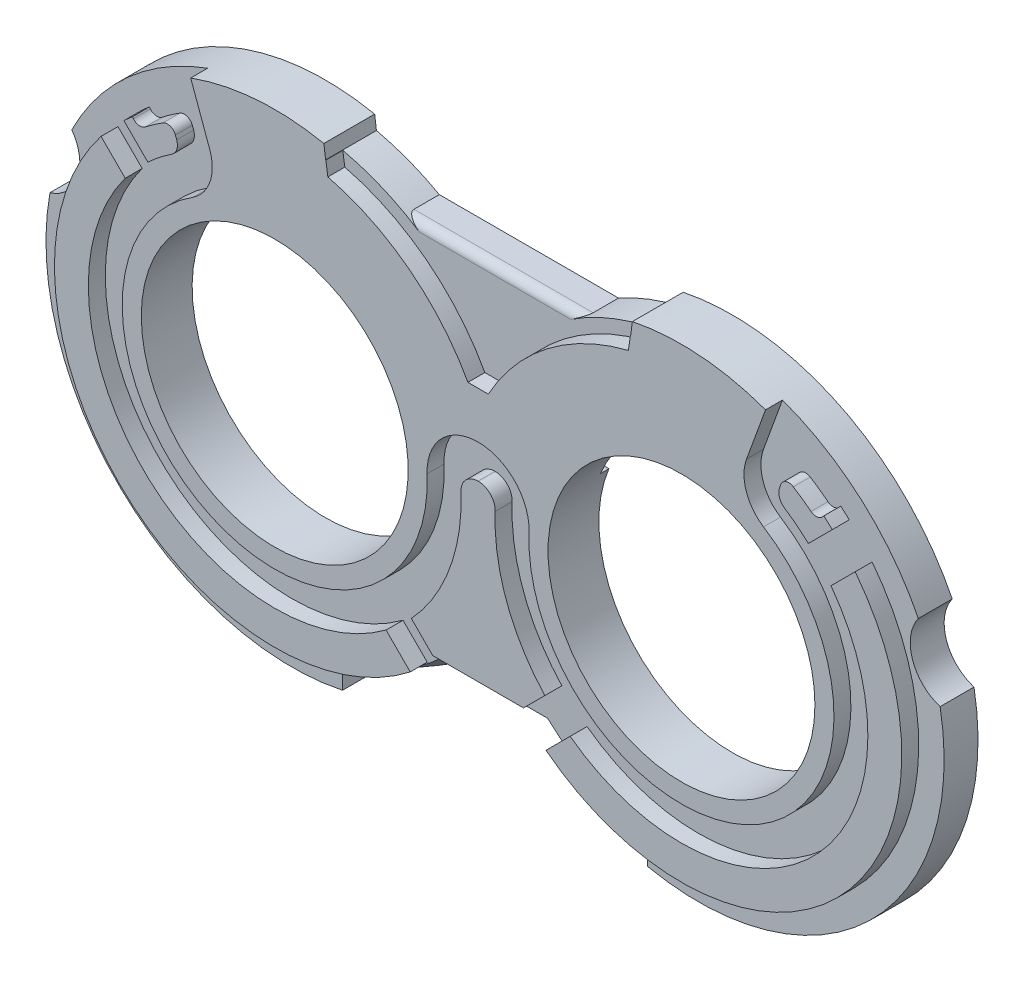
SolidWorks part; units mm, degrees
material "PW70:6:C1:0:1:2:Re:26:"
ref_plane "Plan1" through (0, 0, 0) normal (0, 0, 1) x (1, 0, 0)
ref_plane "Plan2" through (0, 0, 0) normal (0, 1, 0) x (1, 0, 0)
ref_plane "Plan3" through (0, 0, 0) normal (1, 0, 0) x (0, 0, -1)
sketch "Esquisse1" plane through (0, 0, 0) normal (0, 0, 1) x (1, 0, 0)
  line L0 (0, 24) -> (10.5743, 24)
  line L1 (0, -20.5) -> (5.6697, -20.5)
  line L2 (0, 24) -> (0, -20.5)
  line L5 (18, -26.8375) -> (18, -28.3725)
  line L6 (18, 26.8375) -> (18.2039, 28.4149)
  arc A0 (18, 26.8375) -> (10.5743, 24) centre (24, 0) ccw
  circle A1 centre (24, 0) radius 15.75
  arc A2 (5.6697, -20.5) -> (18, -26.8375) centre (24, 0) ccw
  arc A3 (18, -28.3725) -> (52.5259, 5.2222) centre (24, 0) ccw
  arc A4 (49.9541, 12.9378) -> (52.5259, 5.2222) centre (54, 10) ccw
  arc A5 (49.9541, 12.9378) -> (18.2039, 28.4149) centre (24, 0) ccw
  dimension "D1" = 10
  dimension "D3" = 31.5
  dimension "D4" = 54
  dimension "D6" = 55
  dimension "D2" = 24
extrude "Base-Extrusion" add sketch "Esquisse1" along normal blind 6
sketch "Esquisse3" plane through (0, 0, 6) normal (0, 0, 1) x (1, 0, 0)
  line L0 (0, 12.5) -> (0, -20.5)
  line L1 (0, -20.5) -> (8.0078, -20.5)
  line L2 (0, 12.5) -> (1.202, 12.5)
  line L4 (24, 0) -> (60, 0) construction
  line L5 (32.8925, 24.432) -> (33.9186, 27.2511)
  line L6 (18.2039, 28.4149) -> (17.7311, 25.2329)
  arc A0 (8.0078, -20.5) -> (32.8925, 24.432) centre (24, 0) ccw
  arc A1 (33.9186, 27.2511) -> (18.2039, 28.4149) centre (24, 0) ccw
  arc A2 (17.7311, 25.2329) -> (1.202, 12.5) centre (24, 0) ccw
  dimension "D1" = 52
  dimension "D2" = 33
  dimension "D3" = 70
extrude "Enlèv. mat.-Extru.1" cut sketch "Esquisse3" against normal blind 2 flip side to cut
sketch "Esquisse4" plane through (0, 0, 6) normal (0, 0, 1) x (1, 0, 0)
  line L0 (0, 7) -> (0.0208, 7)
  line L1 (10.5743, 24) -> (0, 24) construction
  line L2 (0, 3) -> (0.0208, 3)
  line L3 (24, 0) -> (80, 0) construction
  line L4 (5.351, -17.5) -> (7.8797, -14.9712)
  line L5 (0, -17.5) -> (5.351, -17.5)
  line L6 (8.0078, -20.5) -> (0, -20.5)
  line L7 (0, -20.5) -> (8.0078, -20.5) construction
  line L8 (8.0078, -20.5) -> (10.8617, -17.6461)
  line L9 (32.8925, 24.432) -> (31.6783, 21.096)
  line L10 (0, 7) -> (0, 3)
  line L11 (0, -17.5) -> (0, -20.5)
  line L12 (41.8013, 18.9503) -> (38.9712, 16.1203)
  line L13 (40.6777, 19.7061) -> (40.7942, 19.8483)
  line L14 (41.6461, 13.1383) -> (44.5, 15.9922)
  line L15 (35.724, 20.5161) -> (35.573, 20.1014)
  arc A0 (6.0156, 0.75) -> (33.6862, 15.1716) centre (24, 0) ccw
  arc A1 (2.0191, 0.9167) -> (7.8797, -14.9712) centre (24, 0) ccw
  arc A2 (39.288, 19.5519) -> (37.1953, 21.021) centre (24, 0) ccw
  arc A3 (44.5, 15.9922) -> (41.8013, 18.9503) centre (24, 0) ccw
  arc A4 (10.8617, -17.6461) -> (41.6461, 13.1383) centre (24, 0) ccw
  arc A5 (38.9712, 16.1203) -> (36.1539, 18.338) centre (24, 0) ccw
  arc A6 (40.7942, 19.8483) -> (32.8925, 24.432) centre (24, 0) ccw
  arc A7 (2.0191, 0.9167) -> (0.0208, 3) centre (0.0208, 1) ccw
  arc A8 (6.0156, 0.75) -> (0.0208, 7) centre (0.0208, 1) ccw
  arc A9 (33.6862, 15.1716) -> (31.6783, 21.096) centre (36.3768, 19.3859) cw
  arc A10 (36.1539, 18.338) -> (35.573, 20.1014) centre (36.9826, 19.5883) cw
  arc A13 (37.1953, 21.021) -> (35.724, 20.5161) centre (36.6637, 20.1741) ccw
  arc A14 (40.6777, 19.7061) -> (39.288, 19.5519) centre (39.904, 20.3397) cw
  dimension "D1" = 36
  dimension "D2" = 44
  dimension "D8" = 1
  dimension "D10" = 6
  dimension "D11" = 2
  dimension "D12" = 5
  dimension "D13" = 1.5
  dimension "D3" = 17
  dimension "D4" = 4
  dimension "D5" = 4
  dimension "D6" = 3
  dimension "D7" = 135
  dimension "D9" = 4
extrude "Enlèv. mat.-Extru.2" cut sketch "Esquisse4" against normal blind 2
chamfer "Chanfrein2" distance 3.75 angle 20 2 edges at (11.4289, -24.4585, 4) (2.8348, -20.5, 4) first distance on face at (11.6319, -24.0636, 2) first distance on face at (2.8348, -20.5, 2)
fillet "Congé3" radius 1 1 edges at (5.2871, 24, 4)
sketch "Esquisse5" plane through (0, 0, 0) normal (0, 0, -1) x (-1, 0, 0)
  line L0 (0, -20.5) -> (-6, -20.5)
  line L1 (0, -20.5) -> (-5.6697, -20.5) construction
  line L2 (-6, -20.5) -> (-6, -7.5)
  line L3 (-5, -6.5) -> (0, -6.5)
  line L4 (0, 24) -> (0, -20.5) construction
  line L5 (0, -6.5) -> (0, -20.5)
  line L6 (-10.5743, 24) -> (0, 24) construction
  line L7 (-20, 10) -> (12, 10)
  line L8 (-20, 10) -> (-20, 6)
  line L9 (-20, 6) -> (12, 6)
  line L10 (12, 10) -> (12, 6)
  arc A0 (-6, -7.5) -> (-5, -6.5) centre (-5, -7.5) cw
  dimension "D3" = 1
  dimension "D1" = 6
  dimension "D2" = 14
  dimension "D4" = 4
  dimension "D5" = 14
extrude "Enlèv. mat.-Extru.3" cut sketch "Esquisse5" against normal blind 1
sketch "Esquisse6" plane through (0, 0, 1) normal (0, 0, -1) x (-1, 0, 0)
  line L1 (0, -20.227) -> (-5, -20.227)
  line L2 (0, -20.227) -> (0, -7.227)
  line L3 (0, -7.227) -> (-4.5, -7.227)
  line L4 (-5, -20.227) -> (-5, -7.727)
  arc A0 (-5, -7.727) -> (-4.5, -7.227) centre (-4.5, -7.727) cw
  dimension "D3" = 0.5
  dimension "D1" = 13
  dimension "D2" = 5
extrude "Enlèv. mat.-Extru.4" cut sketch "Esquisse6" against normal blind 0.5
mirror "Bossage-Symétrie1" about plane through (0, 24, 6) normal (1, 0, 0) of bodies 105
